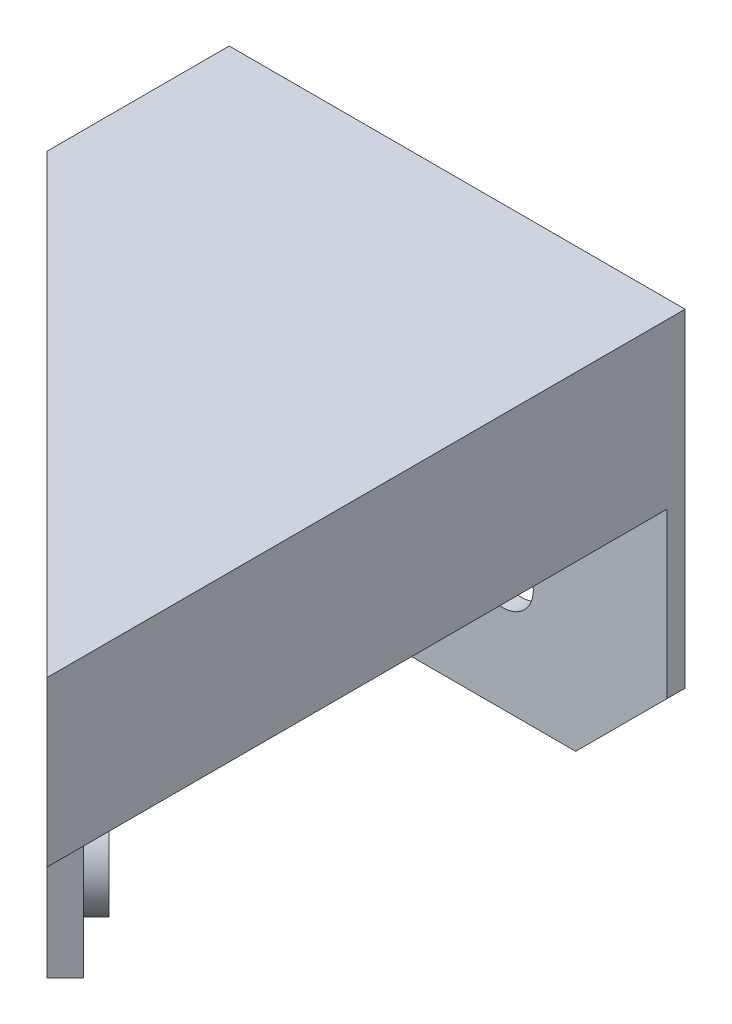
SolidWorks part; units mm, degrees
ref_plane "Front Plane" through (0, 0, 0) normal (0, 0, 1) x (1, 0, 0)
ref_plane "Top Plane" through (0, 0, 0) normal (0, 1, 0) x (1, 0, 0)
ref_plane "Right Plane" through (0, 0, 0) normal (1, 0, 0) x (0, 0, -1)
sketch "Sketch1" plane through (0, 0, 0) normal (0, 0, 1) x (1, 0, 0)
  line L1 (6.2499, -29.45) -> (-16.7501, -29.45)
  line L2 (6.2499, -29.45) -> (6.2499, -6.45)
  line L3 (6.2499, -6.45) -> (-16.7501, -6.45)
  line L4 (-16.7501, -29.45) -> (-16.7501, -6.45)
  point P0 (0, 0)
  point P9 (0, 0)
  dimension "D2" = 23
  dimension "D1" = 23
extrude "Boss-Extrude1" add sketch "Sketch1" along normal blind 1 contours L4 L1 L2 L3 region at (-5.2501, -17.95, 0)
sketch "Sketch4" plane through (-16.7501, 0, 0) normal (-1, 0, 0) x (0, 0, 1)
  line L0 (1, -29.45) -> (0, -29.45) construction
  line L1 (0, -6.45) -> (10, -6.45)
  line L2 (0, -6.45) -> (0, -29.45)
  line L3 (0, -29.45) -> (10, -29.45)
  line L4 (10, -6.45) -> (10, -29.45)
  dimension "D1" = 10
extrude "Boss-Extrude3" add sketch "Sketch4" along normal blind 2
sketch "Sketch5" plane through (0, -29.45, 0) normal (0, -1, 0) x (1, 0, 0)
  line L0 (-18.7501, 10) -> (-2.4866, 26.2635)
  line L1 (-2.4866, 26.2635) -> (-1.4866, 25.2635)
  line L2 (-1.4866, 25.2635) -> (-16.7501, 10)
  line L3 (-16.7501, 1) -> (-16.7501, 10) construction
  line L4 (-16.7501, 10) -> (-18.7501, 10)
  dimension "D1" = 135
  dimension "D2" = 23
extrude "Boss-Extrude4" add sketch "Sketch5" against normal up to surface (23 mm away) up to face at (-9.7501, -6.45, 3.6667)
sketch "Sketch6" plane through (-13.375, 0, 13.375) normal (0.7071, 0, -0.7071) x (-0.7071, 0, -0.7071)
  line L0 (-16.8128, -6.45) -> (-16.8128, -29.45) construction
  line L2 (4.773, -29.45) -> (-16.8128, -29.45) construction
  line L3 (-11.8128, -26.45) -> (-11.8128, -18.45) construction
  circle A1 centre (-11.8128, -26.45) radius 1.675
  circle A2 centre (-11.8128, -18.45) radius 1.675
  dimension "D1" = 8
  dimension "D4" = 5
  dimension "D5" = 3
  dimension "D6" = 3.35
extrude "Cut-Extrude1" cut sketch "Sketch6" against normal blind 2
chamfer "Chamfer1" distance 1 angle 45 1 edges at (-16.7501, -17.95, 1)
sketch "Sketch7" plane through (0, 0, 1) normal (0, 0, 1) x (1, 0, 0)
  line L0 (-18.7501, -6.45) -> (-2.4866, -6.45) construction
  line L1 (-17.7501, -14.45) -> (5.2499, -14.45)
  line L2 (-17.7501, -14.45) -> (-17.7501, -7.45)
  line L3 (-17.7501, -7.45) -> (5.2499, -7.45)
  line L4 (5.2499, -14.45) -> (5.2499, -7.45)
  line L5 (-17.7501, -14.45) -> (5.2499, -7.45) construction
  line L6 (-17.7501, -7.45) -> (5.2499, -14.45) construction
  line L14 (6.2499, -29.45) -> (6.2499, -6.45) construction
  line L15 (-18.7501, -6.45) -> (-18.7501, -29.45) construction
  point P0 (-6.2501, -10.95)
  point P5 (-6.2501, -10.95)
  dimension "D1" = 1
  dimension "D2" = 7
  dimension "D3" = 1
  dimension "D4" = 1
extrude "Cut-Extrude3" cut sketch "Sketch7" against normal up to surface (1 mm away) and the other way up to surface up to face at (-6.2501, -17.95, 0) other way up to face at (-4.8377, -18.45, 23.9123)
sketch "Sketch9" plane through (0, 0, 0) normal (0, 0, -1) x (-1, 0, 0)
  line L0 (-6.2499, -17.95) -> (18.7501, -17.95) construction
  line L1 (-6.2499, -15.45) -> (18.7501, -15.45)
  line L2 (-6.2499, -15.45) -> (-6.2499, -6.45)
  line L3 (-6.2499, -6.45) -> (18.7501, -6.45)
  line L4 (18.7501, -15.45) -> (18.7501, -6.45)
  line L5 (-6.2499, -29.45) -> (-6.2499, -6.45) construction
  line L6 (-5.2499, -14.45) -> (17.7501, -14.45) construction
  line L9 (17.7501, -7.45) -> (-5.2499, -7.45) construction
  line L10 (-5.2499, -7.45) -> (-5.2499, -14.45) construction
  line L11 (-5.2499, -14.45) -> (17.7501, -14.45)
  line L12 (-5.2499, -14.45) -> (-5.2499, -7.45)
  line L13 (-5.2499, -7.45) -> (17.7501, -7.45)
  line L14 (17.7501, -14.45) -> (17.7501, -7.45)
  line L15 (-5.2499, -14.45) -> (17.7501, -7.45) construction
  line L16 (-5.2499, -7.45) -> (17.7501, -14.45) construction
  line L17 (18.7501, -6.45) -> (18.7501, -29.45) construction
  point P0 (12.425, 0)
  point P13 (6.2501, -10.95)
  dimension "D2" = 1
  dimension "D4" = 1
extrude "Boss-Extrude6" add sketch "Sketch9" against normal up to surface (35 mm away) up to face at (-10.3683, -14.45, 18.3817)
sketch "Sketch10" plane through (0, 0, 1) normal (0, 0, 1) x (1, 0, 0)
  line L0 (6.2499, -29.45) -> (-15.7501, -29.45) construction
  line L1 (6.2499, -29.45) -> (6.2499, -15.45) construction
  circle A0 centre (-2.7501, -22.95) radius 1.675
  dimension "D1" = 6.5
  dimension "D2" = 9
  dimension "D3" = 3.35
extrude "Cut-Extrude4" cut sketch "Sketch10" against normal blind 10
sketch "Sketch12" plane through (-13.375, 0, 13.375) normal (0.7071, 0, -0.7071) x (-0.7071, 0, -0.7071)
  circle A0 centre (-11.8128, -18.45) radius 2.975
  circle A1 centre (-11.8128, -18.45) radius 1.675
  circle A2 centre (-11.8128, -26.45) radius 1.675
  circle A3 centre (-11.8128, -26.45) radius 2.975
  circle A4 centre (-11.8128, -18.45) radius 1.675 construction
  dimension "D1" = 1.3
  dimension "D2" = 1.3
extrude "Boss-Extrude8" add sketch "Sketch12" along normal blind 1
chamfer "Chamfer2" distance 5 angle 45 1 edges at (6.2499, -29.45, 0.5)
sketch "Sketch13" plane through (0, 0, 0) normal (0, 0, -1) x (-1, 0, 0)
  line L0 (-5.2499, -7.45) -> (-5.2499, -14.45) construction
  line L1 (-4.2499, -17.45) -> (-1.2499, -17.45)
  line L2 (-4.2499, -17.45) -> (-4.2499, -14.45)
  line L3 (-4.2499, -14.45) -> (-1.2499, -14.45)
  line L4 (-1.2499, -17.45) -> (-1.2499, -14.45)
  line L5 (-4.2499, -17.45) -> (-1.2499, -14.45) construction
  line L6 (-4.2499, -14.45) -> (-1.2499, -17.45) construction
  line L7 (12.7501, -17.45) -> (15.7501, -17.45)
  line L8 (12.7501, -17.45) -> (12.7501, -14.45)
  line L9 (12.7501, -14.45) -> (15.7501, -14.45)
  line L10 (15.7501, -17.45) -> (15.7501, -14.45)
  line L11 (12.7501, -17.45) -> (15.7501, -14.45) construction
  line L12 (12.7501, -14.45) -> (15.7501, -17.45) construction
  line L13 (16.7501, -14.45) -> (16.7501, -7.45) construction
  line L14 (-5.2499, -14.45) -> (17.7501, -14.45) construction
  point P0 (-2.7499, -15.95)
  point P5 (14.2501, -15.95)
  dimension "D1" = 2.5
  dimension "D2" = 2.5
  dimension "D3" = 3
  dimension "D4" = 3
extrude "Boss-Extrude9" add sketch "Sketch13" along normal blind 2
